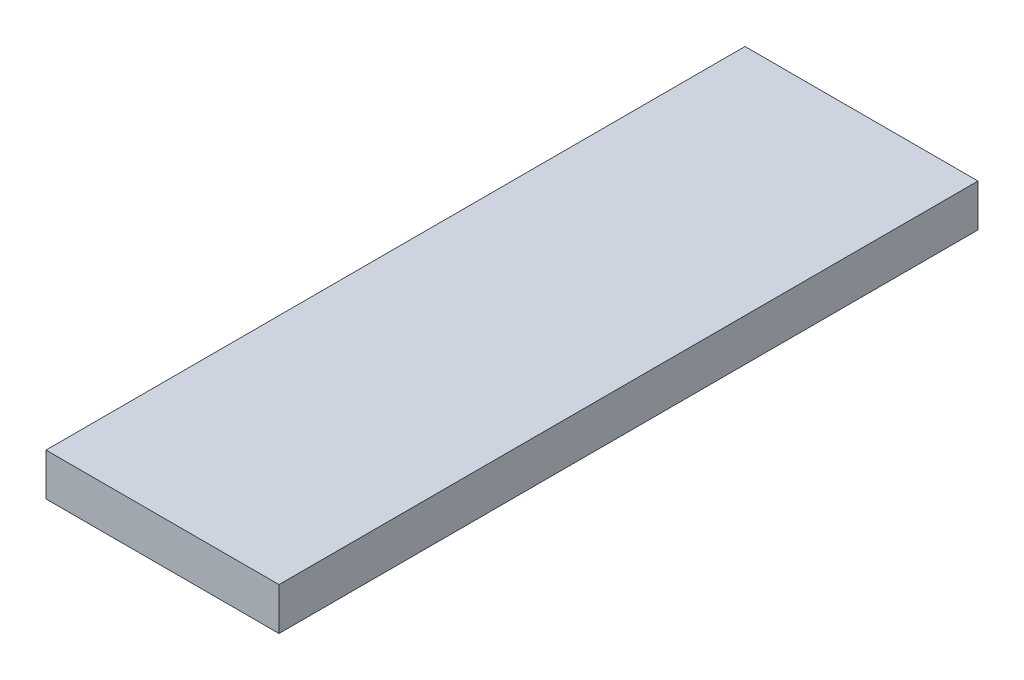
SolidWorks part; units mm, degrees
ref_plane "Front Plane" through (0, 0, 0) normal (0, 0, 1) x (1, 0, 0)
ref_plane "Top Plane" through (0, 0, 0) normal (0, 1, 0) x (1, 0, 0)
ref_plane "Right Plane" through (0, 0, 0) normal (1, 0, 0) x (0, 0, -1)
sketch "Sketch1" plane through (0, 0, 0) normal (0, 1, 0) x (1, 0, 0)
  line L1 (0, 0) -> (55, 0)
  line L2 (0, 0) -> (0, 165)
  line L3 (0, 165) -> (55, 165)
  line L4 (55, 0) -> (55, 165)
  dimension "D1" = 165
  dimension "D2" = 55
extrude "Boss-Extrude1" add sketch "Sketch1" along normal blind 10
ref_axis "Axis1" through (27.5, 0, -165) along (0, 0, 1)
ref_point "Point1"
